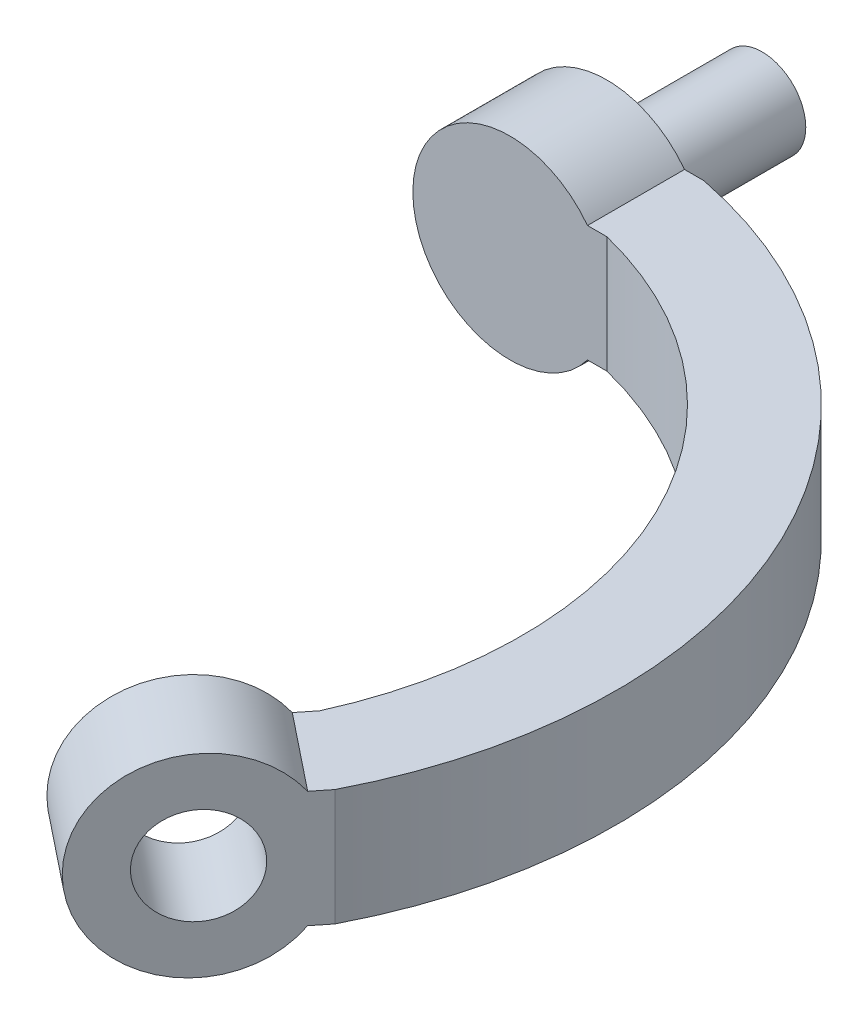
SolidWorks part; units mm, degrees
ref_plane "前视基准面" through (0, 0, 0) normal (0, 0, 1) x (1, 0, 0)
ref_plane "上视基准面" through (0, 0, 0) normal (0, 1, 0) x (1, 0, 0)
ref_plane "右视基准面" through (0, 0, 0) normal (1, 0, 0) x (0, 0, -1)
other "Configuration Table"
sketch "草图2" plane through (0, 0, 0) normal (0, 0, 1) x (1, 0, 0)
  circle A0 centre (0, 0) radius 5
  dimension "D1" = 10
extrude "凸台-拉伸3" add sketch "草图2" along normal blind 5
sketch "草图3" plane through (0, 0, 0) normal (0, 1, 0) x (1, 0, 0)
  line L0 (0, 0) -> (0, -25) construction
  line L1 (0, -25) -> (18.1885, -39.5041) construction
  line L2 (18.7543, -33.5602) -> (22.6635, -36.6775)
  line L3 (0, 0) -> (5, 0)
  line L4 (0, 0) -> (0, -5)
  line L5 (0, -5) -> (5, -5)
  line L6 (5, 0) -> (5, -5)
  line L15 (22.6635, -36.6775) -> (19.5462, -40.5868)
  line L16 (19.5462, -40.5868) -> (15.6369, -37.4694)
  line L17 (15.6369, -37.4694) -> (18.7543, -33.5602)
  arc A0 (5, -5) -> (18.7543, -33.5602) centre (0, -25) cw
  arc A1 (5, 0) -> (22.6635, -36.6775) centre (0, -25) cw
  dimension "D4" = 20
  dimension "D1" = 128.57
  dimension "D2" = 5
  dimension "D3" = 5
  dimension "D5" = 5
extrude "凸台-拉伸4" add sketch "草图3" along normal blind 3 and the other way blind 3 separate body contours A1 L6 A0 L2 region at (18.9524, 0, 15.8727)
revolve "旋转1" add sketch "草图3<3>" angle 360 about L1 region at (19.1502, 0, 37.0735)
sketch "草图3<3>" plane through (0, 0, 0) normal (0, 1, 0) x (1, 0, 0) same geometry as "草图3"
sketch "草图4" plane through (-9.0691, 0, 11.3729) normal (-0.6235, 0, 0.7818) x (0.7818, 0, 0.6235)
  line L4 (40.5868, 3) -> (35.5868, 3)
  line L5 (35.5868, 3) -> (35.5868, -3)
  line L6 (35.5868, -3) -> (40.5868, -3)
  line L7 (40.5868, -3) -> (40.5868, 3)
  line L8 (40.5868, 3) -> (35.5868, 3)
  line L9 (35.5868, 3) -> (35.5868, -3)
  line L10 (35.5868, -3) -> (40.5868, -3)
  line L11 (40.5868, -3) -> (40.5868, 3)
  dimension "D1" = 0
extrude "凸台-拉伸5" add sketch "草图4" along normal blind 3
sketch "草图5" plane through (5, 0, 0) normal (-1, 0, 0) x (0, 0, 1)
  line L4 (5, -3) -> (5, 3)
  line L5 (5, 3) -> (0, 3)
  line L6 (0, 3) -> (0, -3)
  line L7 (0, -3) -> (5, -3)
  line L8 (5, -3) -> (5, 3)
  line L9 (5, 3) -> (0, 3)
  line L10 (0, 3) -> (0, -3)
  line L11 (0, -3) -> (5, -3)
  dimension "D1" = 0
extrude "凸台-拉伸6" add sketch "草图5" along normal blind 3
sketch "草图6" plane through (27.8234, 0, 22.1873) normal (-0.7818, 0, -0.6235) x (-0.6235, 0, 0.7818)
  circle A0 centre (19.5462, 0) radius 2.5
  dimension "D1" = 5
extrude "切除-拉伸1" cut sketch "草图6" against normal blind 5
sketch "草图7" plane through (0, 0, 5) normal (0, 0, 1) x (1, 0, 0)
  circle A0 centre (0, 0) radius 2.25
  dimension "D1" = 4.5
extrude "凸台-拉伸7" add sketch "草图7" against normal blind 8 from surface starting at face at (2.25, 0, 0)
